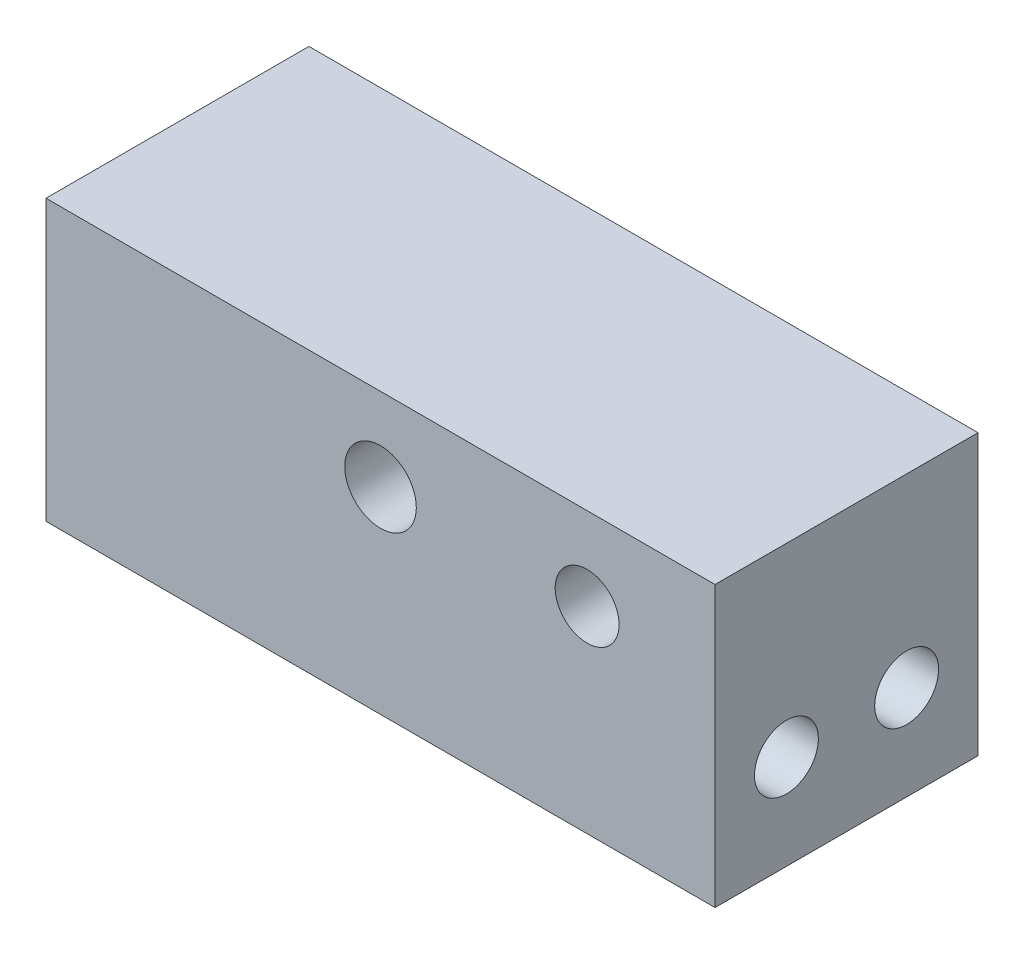
SolidWorks part; units mm, degrees
material "ABS"
ref_plane "X-Y Datum" through (0, 0, 0) normal (0, 0, 1) x (1, 0, 0)
ref_plane "X-Z Datum" through (0, 0, 0) normal (0, 1, 0) x (1, 0, 0)
ref_plane "Y-Z Datum" through (0, 0, 0) normal (1, 0, 0) x (0, 0, -1)
sketch "Sketch1" plane through (0, 0, 0) normal (0, 0, 1) x (1, 0, 0)
  line L1 (-28.275, 11.1125) -> (28.275, 11.1125)
  line L2 (-28.275, 11.1125) -> (-28.275, -11.1125)
  line L3 (-28.275, -11.1125) -> (28.275, -11.1125)
  line L4 (28.275, 11.1125) -> (28.275, -11.1125)
  line L5 (-28.275, 11.1125) -> (28.275, -11.1125) construction
  line L6 (-28.275, -11.1125) -> (28.275, 11.1125) construction
  point P0 (0, 0)
  dimension "D1" = 56.55
  dimension "D2" = 22.225
extrude "Boss-Extrude1" add sketch "Sketch1" along normal blind 22.225 contours L2 L3 L4 L1
sketch "Sketch2" plane through (0, 0, 22.225) normal (0, 0, 1) x (1, 0, 0)
  line L0 (-23.5453, 4.1125) -> (31.0951, 4.1125) construction
  line L1 (0, 11.1125) -> (0, -11.1125) construction
  line L2 (-28.275, 11.1125) -> (28.275, 11.1125) construction
  line L3 (-17.4625, 4.1125) -> (17.4625, 4.1125) construction
  line L4 (-28.275, -11.1125) -> (28.275, -11.1125) construction
  circle A0 centre (17.4625, 4.1125) radius 2.7
  circle A1 centre (-17.4625, 4.1125) radius 2.7 construction
  circle A2 centre (0, 4.1125) radius 3.025
  point P10 (0, 4.1125)
  dimension "D1" = 5.4
  dimension "D4" = 6.05
  dimension "D2" = 34.925
  dimension "D3" = 7
extrude "Cut-Extrude1" cut sketch "Sketch2" against normal blind 10 contours A1 L0 L3 | L0 A1 L3 | L0 L3 A0 | L3 L0 A0 | A2 region at (17.4625, 4.1125, 22.225) region at (0, 4.1125, 22.225)
sketch "Sketch3" plane through (-28.275, 0, 0) normal (-1, 0, 0) x (0, 0, 1)
  line L0 (0, -4.5375) -> (22.225, -4.5375) construction
  line L1 (0, 11.1125) -> (0, -11.1125) construction
  line L2 (22.225, 184.8875) -> (22.225, -15.7125) construction
  line L3 (16.1925, -4.5375) -> (6.0325, -4.5375) construction
  line L4 (11.1125, 11.1125) -> (11.1125, -11.1125) construction
  line L5 (22.225, 11.1125) -> (0, 11.1125) construction
  line L6 (22.225, -11.1125) -> (0, -11.1125) construction
  line L7 (-277.475, -12.5375) -> (22.225, -12.5375) construction
  circle A0 centre (16.1925, -4.5375) radius 2.7
  circle A1 centre (6.0325, -4.5375) radius 2.7
  point P10 (11.1125, -4.5375)
  dimension "D1" = 5.4
  dimension "D2" = 10.16
  dimension "D3" = 8
extrude "Cut-Extrude2" cut sketch "Sketch3" against normal blind 8
sketch "Sketch5" plane through (0, -11.1125, 0) normal (0, -1, 0) x (1, 0, 0)
  line L4 (-28.275, 0) -> (28.275, 0)
  line L5 (28.275, 0) -> (28.275, 22.225)
  line L6 (28.275, 22.225) -> (-28.275, 22.225)
  line L7 (-28.275, 22.225) -> (-28.275, 0)
  line L8 (-28.275, 0) -> (28.275, 0)
  line L9 (28.275, 0) -> (28.275, 22.225)
  line L10 (28.275, 22.225) -> (-28.275, 22.225)
  line L11 (-28.275, 22.225) -> (-28.275, 0)
  dimension "D1" = 0
extrude "Boss-Extrude2" add sketch "Sketch5" along normal blind 1.4249
mirror "Mirror2" about plane through (0, 0, 0) normal (1, 0, 0) of "Cut-Extrude2"
sketch "Sketch6" plane through (0, 0, 0) normal (0, 0, -1) x (-1, 0, 0)
  line L0 (-28.275, 1.1125) -> (28.275, 1.1125) construction
  line L1 (-28.275, 11.1125) -> (-28.275, -12.5374) construction
  line L2 (28.275, 11.1125) -> (28.275, -12.5374) construction
  line L3 (-10, 1.1125) -> (10, 1.1125) construction
  line L5 (28.275, 11.1125) -> (-28.275, 11.1125) construction
  circle A1 centre (-10, 1.1125) radius 3.025
  circle A2 centre (10, 1.1125) radius 3.025
  point P10 (0, 1.1125)
  dimension "D1" = 6.05
  dimension "D2" = 10
  dimension "D3" = 20
extrude "Cut-Extrude3" cut sketch "Sketch6" against normal blind 10
